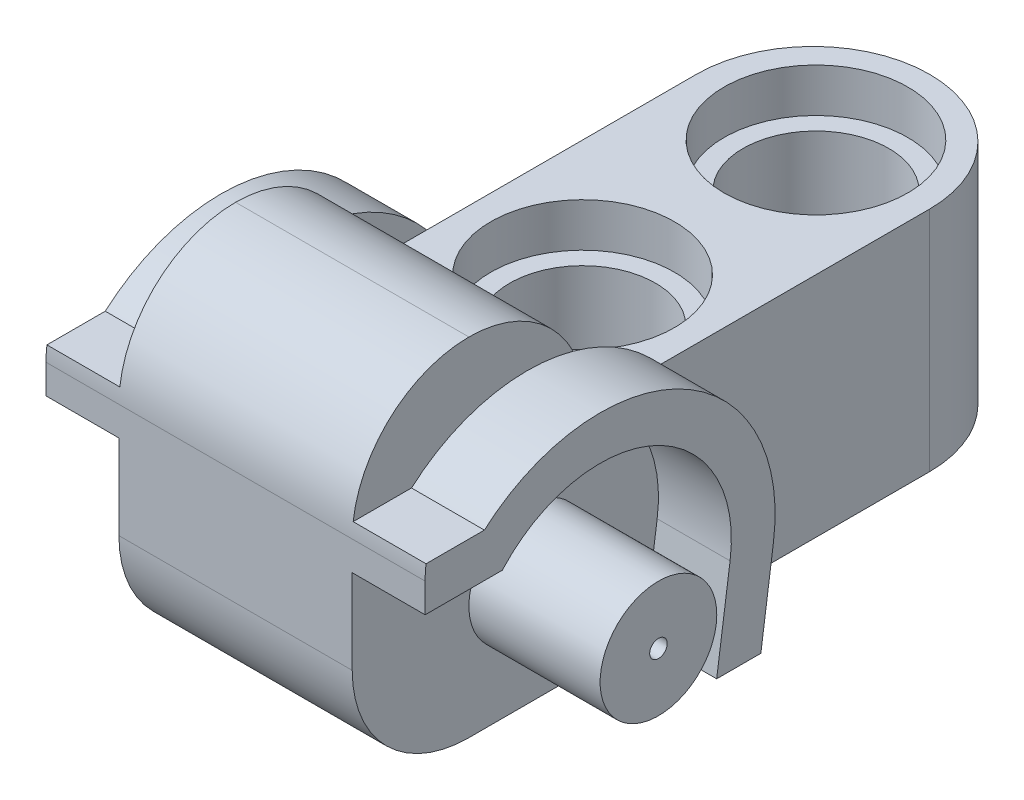
SolidWorks part; units mm, degrees
ref_plane "前视基准面" through (0, 0, 0) normal (0, 0, 1) x (1, 0, 0)
ref_plane "上视基准面" through (0, 0, 0) normal (0, 1, 0) x (1, 0, 0)
ref_plane "右视基准面" through (0, 0, 0) normal (1, 0, 0) x (0, 0, -1)
other "Configuration Table"
sketch "草图2" plane through (0, 0, 0) normal (1, 0, 0) x (0, 0, -1)
  line L0 (-6, 0) -> (17.8, 0) construction
  line L1 (-6, 8) -> (17.8, 8)
  line L2 (-6, 8) -> (-6, -8)
  line L3 (-6, -8) -> (17.8, -8)
  line L4 (17.8, 8) -> (17.8, -8)
  line L5 (2, 8) -> (2, -8)
  line L6 (4.4562, -0.6263) -> (3.4199, -8)
  line L7 (0, -4.5) -> (-6, -4.5)
  line L8 (0, -4.5) -> (0, 3)
  line L9 (0, 3) -> (-6, 3)
  line L10 (-6, -4.5) -> (-6, 3)
  line L12 (0, 4.5) -> (-6, 4.5)
  line L13 (4.9346, -8) -> (5.9416, -0.835)
  line L14 (0, 3.9) -> (17.8, 3.9)
  line L15 (0, 3.9) -> (0, -3.9)
  line L16 (0, -3.9) -> (17.8, -3.9)
  line L17 (17.8, 3.9) -> (17.8, -3.9)
  circle A0 centre (0, 0) radius 2
  circle A1 centre (0, 0) radius 4.5
  circle A2 centre (0, 0) radius 6
  dimension "D1" = 4
  dimension "D3" = 9
  dimension "D7" = 7.8
  dimension "D2" = 7.5
  dimension "D4" = 6
  dimension "D5" = 16
  dimension "D6" = 15.8
  dimension "D8" = 82
extrude "凸台-拉伸1" add sketch "草图2" along normal blind 4 contours L1 L4 L3 L2
extrude "凸台-拉伸3" add sketch "草图2<10>" along normal blind 4.5 from surface contours A0 L0 L8 | L8 L0 A0 | L0 L15 A0 | L0 A0 L15 region at (0, -0.8488, -0.8488) region at (0, 0.8488, -0.8488) region at (0, -0.8488, 0.8488) region at (0, 0.8488, 0.8488) starting at face at (4, 0, -5.9)
sketch "草图2<10>" plane through (0, 0, 0) normal (1, 0, 0) x (0, 0, -1) same geometry as "草图2"
sketch "草图5" plane through (8.5, 0, 0) normal (1, 0, 0) x (0, 0, -1)
  circle A0 centre (0, 0) radius 0.3
  dimension "D1" = 0.6
extrude "切除-拉伸10" cut sketch "草图5" against normal blind 1
extrude "切除-拉伸5" cut sketch "草图2<9>" along normal through all contours L14 A1 L5 | L14 A2 L5 A1 | A2 L14 L4 L1 L5 | L5 A2 L6 L16 A1 | A2 L5 L3 L6 | L6 A2 L16 | A2 L6 L3 L13 L16 | L16 L13 L3 L4 region at (0, 6.0106, -10.2) region at (0, 4.5465, -2.9335) region at (0, 3.9443, -2.0827) region at (0, -5.9657, -11.5103) region at (0, -6.0095, -4.4754) region at (0, -6.5236, -2.8792) region at (0, -4.5801, -2.836) region at (0, -4.1252, -4.1579)
sketch "草图2<9>" plane through (0, 0, 0) normal (1, 0, 0) x (0, 0, -1) same geometry as "草图2"
extrude "凸台-拉伸2" add sketch "草图2<4>" along normal blind 2.5 from surface contours A2 L6 L3 L13 L16 | L6 A2 L16 | L0 A1 L6 L16 A2 | A2 L16 L13 | A1 L0 A2 L14 | L14 A2 L5 A1 | L5 A2 L12 A1 | L12 A2 L9 A1 | A2 L12 L2 L9 region at (0, 2.0799, -4.6295) region at (0, -1.7305, -4.9664) region at (0, 4.5465, -2.9335) region at (0, 5.11, 0.4284) region at (0, -3.1563, -5.3367) region at (0, -4.1252, -4.1579) region at (0, 3.8249, 3.3838) region at (0, -6.0095, -4.4754) region at (0, 3.8627, 5.2791) starting at face at (4, 0, -2)
sketch "草图2<4>" plane through (0, 0, 0) normal (1, 0, 0) x (0, 0, -1) same geometry as "草图2"
mirror "镜向1" about plane through (0, 0, 0) normal (1, 0, 0) of bodies 107
sketch "草图3" plane through (0, 3.9, 0) normal (0, 1, 0) x (1, 0, 0)
  line L0 (4, 2) -> (-4, 2) construction
  line L1 (0, 17.8) -> (0, 2) construction
  line L2 (4, 17.8) -> (-4, 17.8) construction
  circle A0 centre (0, 5.9) radius 2.5
  circle A1 centre (0, 5.9) radius 3.15
  circle A2 centre (0, 13.9) radius 2.5
  circle A3 centre (0, 13.9) radius 3.15
  circle A4 centre (0, 5.9) radius 3.9
  dimension "D1" = 5
  dimension "D2" = 6.3
  dimension "D4" = 7.8
  dimension "D3" = 8
extrude "切除-拉伸6" cut sketch "草图3" against normal through all both and the other way through all contours A2 L1 | L1 A2 | A0 L1 | L1 A0 region at (1.061, 3.9, -13.9) region at (-1.061, 3.9, -13.9) region at (1.061, 3.9, -5.9) region at (-1.061, 3.9, -5.9)
extrude "切除-拉伸7" cut sketch "草图3<4>" against normal blind 1.5 contours L1 A1 A0 | A1 L1 A0 | L1 A3 A2 | A3 L1 A2 region at (2.1776, 3.9, -16.0776) region at (-0.0704, 3.9, -16.725) region at (2.1776, 3.9, -8.0776) region at (-0.0704, 3.9, -8.725)
sketch "草图3<4>" plane through (0, 3.9, 0) normal (0, 1, 0) x (1, 0, 0) same geometry as "草图3"
extrude "切除-拉伸8" cut sketch "草图3<5>" along normal blind 1.5 from surface contours L1 A1 A0 | A1 L1 A0 | L1 A3 A2 | A3 L1 A2 region at (2.1776, 3.9, -16.0776) region at (-0.0704, 3.9, -16.725) region at (2.1776, 3.9, -8.0776) region at (-0.0704, 3.9, -8.725) starting at face at (0, -3.9, -11.4)
sketch "草图3<5>" plane through (0, 3.9, 0) normal (0, 1, 0) x (1, 0, 0) same geometry as "草图3"
sketch "草图4" plane through (0, 0, 0) normal (1, 0, 0) x (0, 0, -1)
  line L0 (5.9416, -0.835) -> (4.9346, -8) construction
  line L1 (-6, -8) -> (5.5109, -8)
  line L2 (-6, -8) -> (-6, -3.9)
  line L3 (-6, -3.9) -> (5.5109, -3.9)
  line L4 (5.5109, -8) -> (5.5109, -3.9)
  line L5 (5.5109, -3.9) -> (17.8, -3.9) construction
  line L6 (-6, 3) -> (-6, -8) construction
  line L7 (4.9346, -8) -> (3.4199, -8) construction
extrude "切除-拉伸9" cut sketch "草图4" against normal through all both and the other way through all
fillet "圆角1" radius 4 5 edges at (0, 8, -2) (-4, 0, -17.8) (4, 0, -17.8) (0, 8, 6) (0, -3.9, 6)
